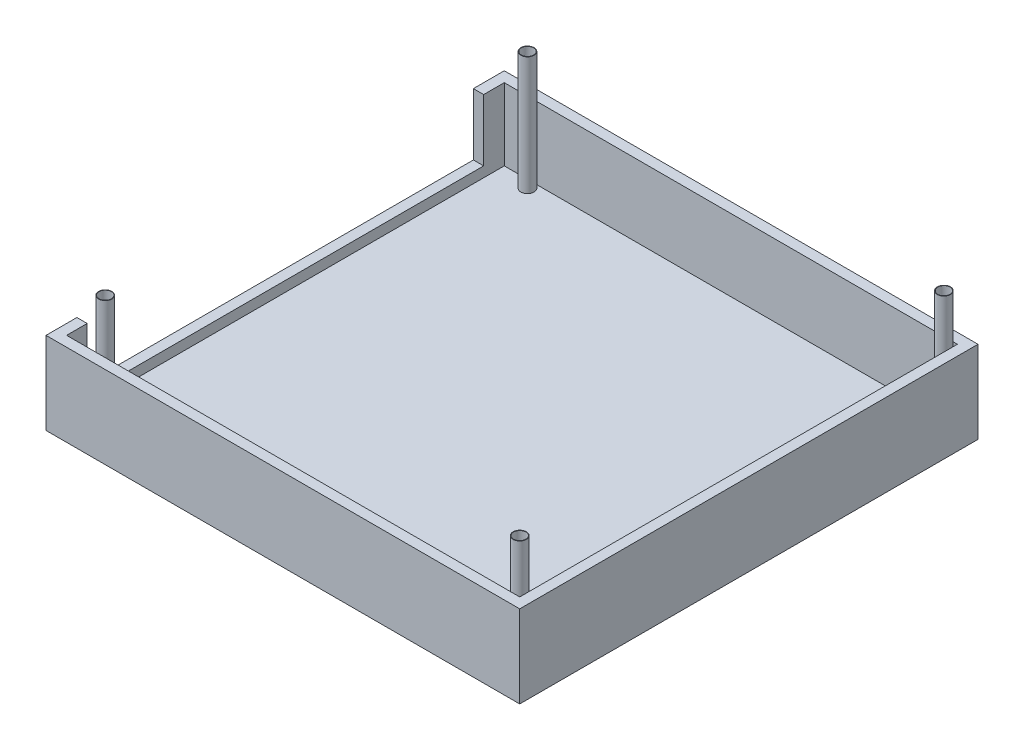
SolidWorks part; units mm, degrees
ref_plane "Piano frontale" through (0, 0, 0) normal (0, 0, 1) x (1, 0, 0)
ref_plane "Piano superiore" through (0, 0, 0) normal (0, 1, 0) x (1, 0, 0)
ref_plane "Piano destro" through (0, 0, 0) normal (1, 0, 0) x (0, 0, -1)
sketch "Schizzo1" plane through (0, 0, 0) normal (0, 1, 0) x (1, 0, 0)
  line L1 (-23, -22.25) -> (23, -22.25)
  line L2 (-23, -22.25) -> (-23, 22.25)
  line L3 (-23, 22.25) -> (23, 22.25)
  line L4 (23, -22.25) -> (23, 22.25)
  line L5 (-23, -22.25) -> (23, 22.25) construction
  line L6 (-23, 22.25) -> (23, -22.25) construction
  point P0 (0, 0)
  dimension "D1" = 44.5
  dimension "D2" = 46
extrude "Estrusione-Estrusione1" add sketch "Schizzo1" along normal blind 8 contours L1 L4 L3 L2
sketch "Schizzo2" plane through (-23, 0, -0.75) normal (1, 0, 0) x (0, 0, -1)
  line L6 (-23, 8) -> (21.5, 8) construction
  line L7 (18.5, 8) -> (-20, 8)
  line L8 (18.5, 8) -> (18.5, 2)
  line L9 (18.5, 2) -> (-20, 2)
  line L10 (-20, 8) -> (-20, 2)
  line L11 (-23, 0) -> (21.5, 0) construction
  dimension "D2" = 3
  dimension "D1" = 3
  dimension "D3" = 2
extrude "Taglio-Estrusione1" cut sketch "Schizzo2" along normal blind 1
shell "Svuota1" thickness 1 removed face at (-22, 5, 0) removed face at (-11.25, 8, 0)
sketch "Schizzo3" plane through (0, 1, 0) normal (0, 1, 0) x (1, 0, 0)
  line L0 (-22, -21.25) -> (-22, -19.25) construction
  line L1 (-22, 21.25) -> (22, 21.25) construction
  line L2 (-22, -21.25) -> (22, -21.25) construction
  line L3 (22, -21.25) -> (22, 21.25) construction
  line L4 (-22, -21.25) -> (22, -21.25) construction
  circle A0 centre (-19, 20.5) radius 0.645
  circle A1 centre (21.3356, 20.5993) radius 0.645
  circle A2 centre (21.34, -20.59) radius 0.645
  circle A3 centre (-19, -20.5) radius 0.645
  point P12 (0, 0)
  point P17 (0, 0)
  point P20 (0, 0)
  point P25 (0, 0)
  point P26 (0, 0)
  point P28 (22, 20.1954)
  dimension "D1" = 1.29
  dimension "D2" = 1.29
  dimension "D3" = 1.29
  dimension "D4" = 1.29
  dimension "D5" = 3
  dimension "D6" = 0.75
  dimension "D7" = 0.75
  dimension "D8" = 3
  dimension "D9" = 0.66
  dimension "D10" = 0.66
  dimension "D11" = 0.6507
  dimension "D12" = 0.6644
extrude "Estrusione-Estrusione3" add sketch "Schizzo3" along normal blind 11.5
hole_wizard "Foro per Vite M1-1" positions "Schizzo4" profile "Schizzo5" hole size "M1" standard "AS"
sketch "Schizzo4" plane through (0, 12.5, 0) normal (0, 1, 0) x (1, 0, 0)
  circle A0 centre (-19, 20.5) radius 0.645 construction
  circle A1 centre (21.3356, 20.5993) radius 0.645 construction
  circle A2 centre (21.34, -20.59) radius 0.645 construction
  circle A3 centre (-19, -20.5) radius 0.645 construction
  point P0 (-19, 20.5)
  point P3 (21.3356, 20.5993)
  point P6 (21.34, -20.59)
  point P9 (-19, -20.5)
  point P12 (0, 0)
  point P15 (0, 0)
  point P16 (0, 0)
  point P19 (0, 0)
  point P20 (0, 0)
  point P23 (0, 0)
  point P24 (0, 0)
sketch "Schizzo5" plane through (-19, 12.5, -20.5) normal (1, 0, 0) x (0, 0, 1)
  line L0 (0, 0) -> (0, 11.8595)
  line L1 (0, 11.8595) -> (0.6, 11.499)
  line L2 (0.6, 11.499) -> (0.6, 0)
  line L5 (0.6, 0) -> (0, 0)
  line L10 (0, 11.8595) -> (-0.6, 11.499) construction
  line L11 (0, -6.35) -> (0, 107.95) construction
  dimension "Hole Dia." = 1.2
  dimension "Hole Depth" = 11.499
  dimension "Drill Angle" = 118
